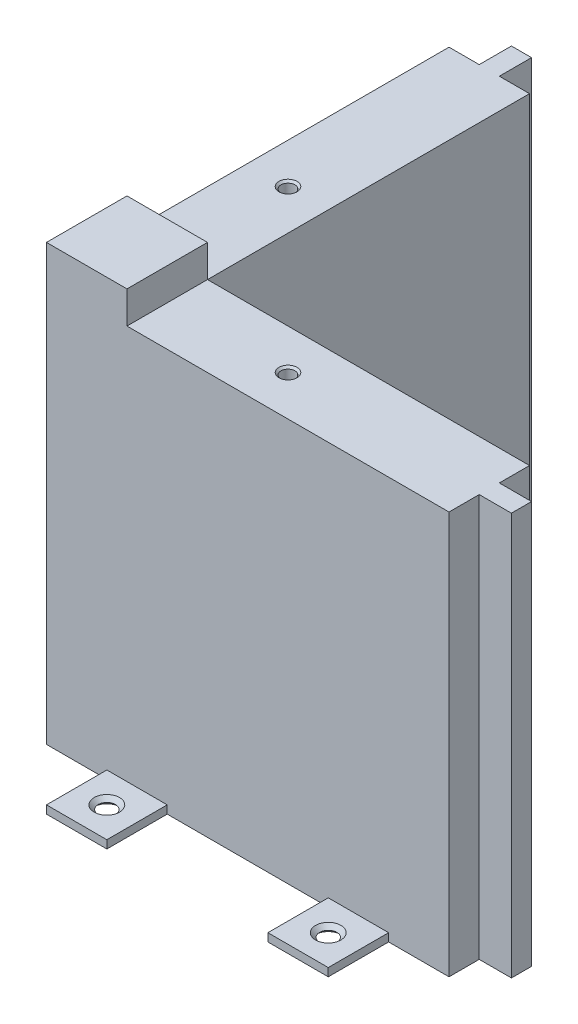
SolidWorks part; units mm, degrees
ref_plane "Front Plane" through (0, 0, 0) normal (0, 0, 1) x (1, 0, 0)
ref_plane "Top Plane" through (0, 0, 0) normal (0, 1, 0) x (1, 0, 0)
ref_plane "Right Plane" through (0, 0, 0) normal (1, 0, 0) x (0, 0, -1)
sketch "Sketch2" plane through (0, 0, 0) normal (0, 1, 0) x (1, 0, 0)
  line L0 (0, 0) -> (0, 100)
  line L1 (0, 0) -> (100, 0)
  line L2 (0, 100) -> (20, 100)
  line L3 (100, 0) -> (100, 20)
  line L4 (100, 20) -> (20, 20)
  line L5 (20, 20) -> (20, 100)
extrude "Boss-Extrude1" add sketch "Sketch2" along normal blind 100
sketch "Sketch3" plane through (0, 100, 0) normal (0, 1, 0) x (1, 0, 0)
  line L0 (20, 20) -> (0, 20)
  line L1 (0, 100) -> (0, 0) construction
  line L2 (0, 20) -> (0, 0)
  line L3 (0, 0) -> (20, 0)
  line L4 (0, 0) -> (100, 0) construction
  line L5 (20, 0) -> (20, 20)
extrude "Boss-Extrude2" add sketch "Sketch3" along normal blind 8
sketch "Sketch4" plane through (100, 0, 0) normal (1, 0, 0) x (0, 0, -1)
  line L0 (7.5, 100) -> (12.5, 100)
  line L1 (0, 100) -> (20, 100) construction
  line L2 (12.5, 100) -> (12.5, 0)
  line L3 (0, 0) -> (20, 0) construction
  line L4 (12.5, 0) -> (7.5, 0)
  line L5 (7.5, 0) -> (7.5, 100)
  line L6 (20, 100) -> (20, 0) construction
  dimension "D1" = 5
  dimension "D2" = 7.5
extrude "Boss-Extrude3" add sketch "Sketch4" along normal blind 8
sketch "Sketch5" plane through (0, 0, -100) normal (0, 0, -1) x (-1, 0, 0)
  line L0 (-12.5, 100) -> (-7.5, 100)
  line L1 (-20, 100) -> (0, 100) construction
  line L2 (-7.5, 100) -> (-7.5, 0)
  line L3 (-20, 0) -> (0, 0) construction
  line L4 (-12.5, 100) -> (-12.5, 0)
  line L5 (-12.5, 0) -> (-7.5, 0)
  line L6 (0, 100) -> (0, 0) construction
  dimension "D1" = 5
  dimension "D2" = 7.5
extrude "Boss-Extrude4" add sketch "Sketch5" along normal blind 8
sketch "Sketch6" plane through (0, 100, 0) normal (0, 1, 0) x (1, 0, 0)
  line L0 (20, 0) -> (100, 0) construction
  line L1 (0, 100) -> (0, 20) construction
  line L2 (20, 20) -> (0, 20) construction
  line L3 (20, 0) -> (20, 20) construction
  circle A0 centre (50, 10) radius 1.75
  circle A1 centre (10, 50) radius 1.75
  dimension "D1" = 3.5
  dimension "D2" = 3.5
  dimension "D3" = 10
  dimension "D4" = 10
  dimension "D5" = 30
  dimension "D6" = 30
extrude "Cut-Extrude1" cut sketch "Sketch6" against normal blind 8
chamfer "Chamfer1" distance 0.5 angle 45 2 edges at (10, 100, -48.25) (50, 100, -8.25)
sketch "Sketch7" plane through (0, 0, 0) normal (0, 0, 1) x (1, 0, 0)
  line L0 (30, 0) -> (30, 2)
  line L1 (0, 0) -> (100, 0) construction
  line L2 (30, 2) -> (15, 2)
  line L3 (15, 2) -> (15, 0)
  line L4 (15, 0) -> (30, 0)
  line L5 (70, 0) -> (70, 2)
  line L6 (70, 2) -> (85, 2)
  line L7 (85, 2) -> (85, 0)
  line L8 (85, 0) -> (70, 0)
  line L9 (0, 108) -> (0, 0) construction
  line L10 (100, 100) -> (100, 0) construction
  dimension "D1" = 15
  dimension "D2" = 15
  dimension "D3" = 2
  dimension "D4" = 2
  dimension "D5" = 15
  dimension "D6" = 15
extrude "Boss-Extrude5" add sketch "Sketch7" along normal blind 15
sketch "Sketch8" plane through (0, 0, 0) normal (-1, 0, 0) x (0, 0, 1)
  line L0 (-85, 0) -> (-85, 2)
  line L1 (-100, 0) -> (0, 0) construction
  line L2 (-85, 2) -> (-70, 2)
  line L3 (-70, 2) -> (-70, 0)
  line L4 (-70, 0) -> (-85, 0)
  line L5 (-30, 0) -> (-30, 2)
  line L6 (-30, 2) -> (-15, 2)
  line L7 (-15, 2) -> (-15, 0)
  line L8 (-15, 0) -> (-30, 0)
  line L9 (-100, 0) -> (-100, 100) construction
  line L10 (0, 108) -> (0, 0) construction
  dimension "D1" = 2
  dimension "D2" = 15
  dimension "D3" = 15
  dimension "D4" = 15
  dimension "D5" = 15
  dimension "D6" = 2
extrude "Boss-Extrude6" add sketch "Sketch8" along normal blind 15
sketch "Sketch9" plane through (0, 2, 0) normal (0, 1, 0) x (1, 0, 0)
  line L0 (70, -15) -> (70, 0) construction
  line L1 (85, -15) -> (70, -15) construction
  line L2 (30, -15) -> (30, 0) construction
  line L3 (30, -15) -> (15, -15) construction
  line L4 (-15, 15) -> (-15, 30) construction
  line L5 (-15, 15) -> (0, 15) construction
  line L6 (-15, 70) -> (-15, 85) construction
  line L7 (-15, 70) -> (0, 70) construction
  circle A0 centre (-7.5, 77.5) radius 2.15
  circle A1 centre (-7.5, 22.5) radius 2.15
  circle A2 centre (22.5, -7.5) radius 2.15
  circle A3 centre (77.5, -7.5) radius 2.15
  dimension "D1" = 4.3
  dimension "D2" = 4.3
  dimension "D3" = 4.3
  dimension "D4" = 4.3
  dimension "D5" = 7.5
  dimension "D6" = 7.5
  dimension "D7" = 7.5
  dimension "D8" = 7.5
  dimension "D9" = 7.5
  dimension "D10" = 7.5
  dimension "D11" = 7.5
  dimension "D12" = 7.5
extrude "Cut-Extrude2" cut sketch "Sketch9" against normal blind 15
chamfer "Chamfer2" distance 1 angle 45 7 edges at (-7.5, 0, -75.35) (-7.5, 2, -75.35) (77.5, 0, 9.65) (77.5, 2, 9.65) (22.5, 0, 9.65) (22.5, 2, 9.65) (-7.5, 2, -20.35)
